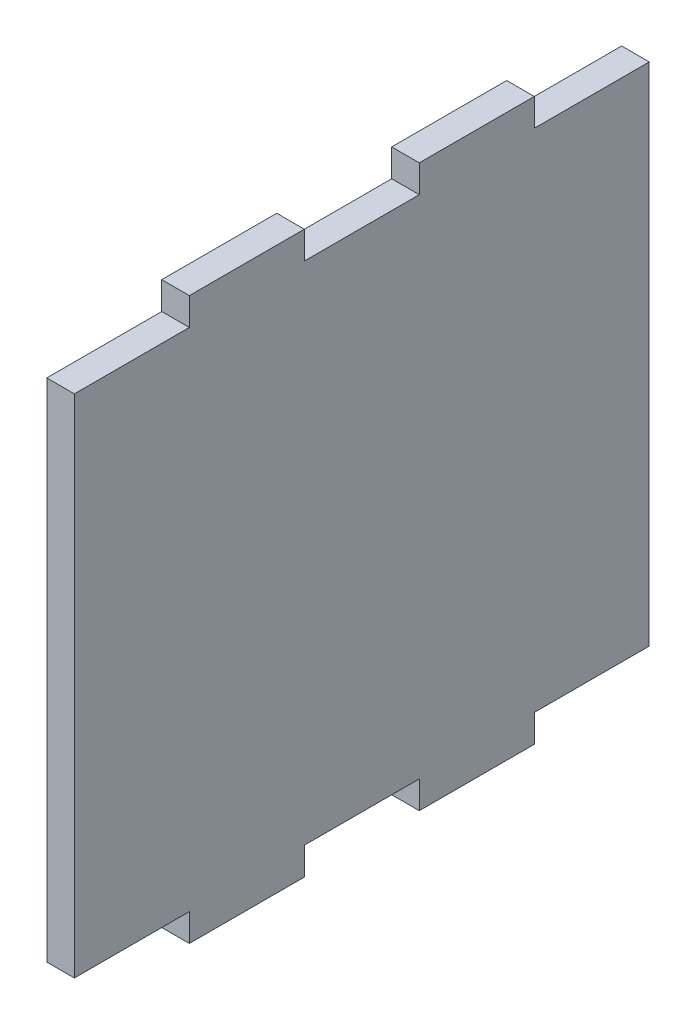
SolidWorks part; units mm, degrees
ref_plane "Front Plane" through (0, 0, 0) normal (0, 0, 1) x (1, 0, 0)
ref_plane "Top Plane" through (0, 0, 0) normal (0, 1, 0) x (1, 0, 0)
ref_plane "Right Plane" through (0, 0, 0) normal (1, 0, 0) x (0, 0, -1)
sketch "Sketch1" plane through (0, 0, 0) normal (1, 0, 0) x (0, 0, -1)
  line L1 (0, 0) -> (125, 0)
  line L2 (0, 0) -> (0, 122)
  line L3 (0, 122) -> (125, 122)
  line L4 (125, 0) -> (125, 122)
sketch "Sketch2" plane through (0, 0, 0) normal (1, 0, 0) x (0, 0, -1)
  line L0 (0, 116) -> (25, 116)
  line L1 (0, 0) -> (0, 122) construction
  line L2 (25, 116) -> (25, 122)
  line L3 (0, 122) -> (125, 122) construction
  line L4 (25, 122) -> (50, 122)
  line L5 (50, 122) -> (50, 116)
  line L6 (50, 116) -> (75, 116)
  line L7 (75, 116) -> (75, 122)
  line L8 (75, 122) -> (100, 122)
  line L9 (100, 122) -> (100, 116)
  line L10 (100, 116) -> (125, 116)
  line L11 (125, 0) -> (125, 122) construction
  line L12 (125, 116) -> (125, 130)
  line L13 (125, 130) -> (0, 130)
  line L14 (0, 130) -> (0, 116)
  line L16 (0, -8) -> (0, 6)
  line L17 (125, -8) -> (0, -8)
  line L18 (125, 6) -> (125, -8)
  line L19 (100, 6) -> (125, 6)
  line L20 (100, 0) -> (100, 6)
  line L21 (75, 0) -> (100, 0)
  line L22 (75, 6) -> (75, 0)
  line L23 (50, 6) -> (75, 6)
  line L24 (50, 0) -> (50, 6)
  line L25 (25, 0) -> (50, 0)
  line L26 (25, 6) -> (25, 0)
  line L27 (0, 6) -> (25, 6)
extrude "Boss-Extrude1" add sketch "Sketch1" along normal blind 6
extrude "Cut-Extrude1" cut sketch "Sketch2" along normal blind 6
